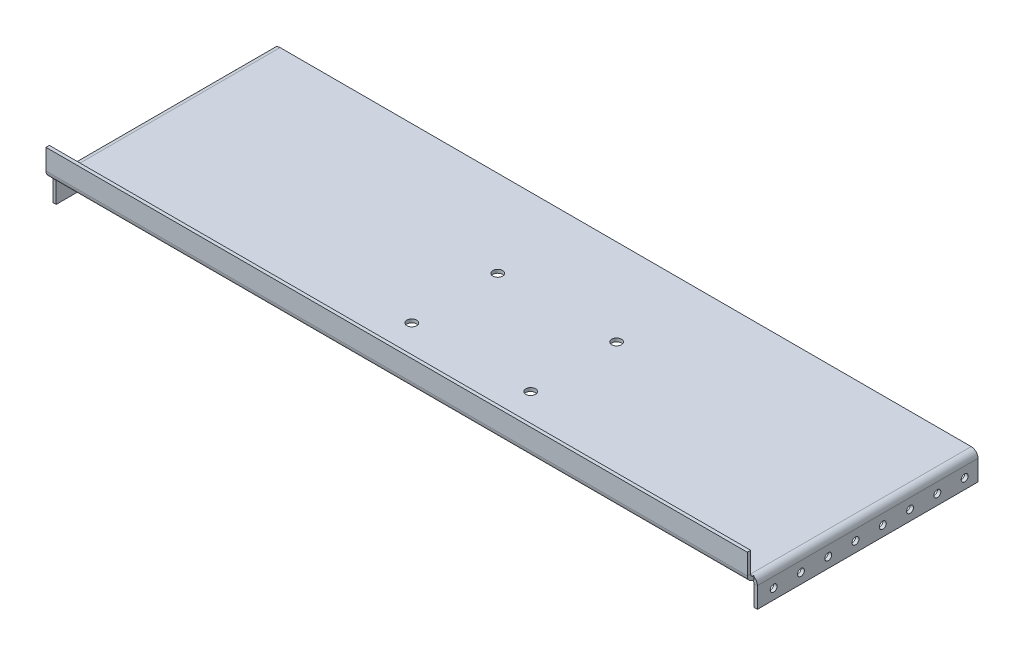
SolidWorks part; units mm, degrees
note: The reader was unsure of these and kept them because the rebuilt part matched: flange length of "Edge-Flange1", "Edge-Flange2", "Edge-Flange3".
ref_plane "Front Plane" through (0, 0, 0) normal (0, 0, 1) x (1, 0, 0)
ref_plane "Top Plane" through (0, 0, 0) normal (0, 1, 0) x (1, 0, 0)
ref_plane "Right Plane" through (0, 0, 0) normal (1, 0, 0) x (0, 0, -1)
sketch "Sketch1" plane through (0, 0, 0) normal (0, 1, 0) x (1, 0, 0)
  line L1 (244.844, -88.9) -> (-244.844, -88.9)
  line L2 (244.844, -88.9) -> (244.844, 88.9)
  line L3 (244.844, 88.9) -> (-244.844, 88.9)
  line L4 (-244.844, -88.9) -> (-244.844, 88.9)
  line L5 (244.844, -88.9) -> (-244.844, 88.9) construction
  line L6 (244.844, 88.9) -> (-244.844, -88.9) construction
  point P0 (0, 0)
  dimension "D1" = 489.688
  dimension "D2" = 177.8
base flange "Base-Flange1" sketch "Sketch1" thickness 2.3622 reverse thickness direction no parameters "D1"=10
edge flange "Edge-Flange1" sketch "Sketch8" flange angle 90 flange length 19.05 flange position material inside bend radius 2.36 thickness 2.3622 relief rectangular parameters "D6"=10
sketch "Sketch8" plane through (0, 0, 88.9) normal (0, 0, 1) x (1, 0, 0)
  line L2 (-244.844, 0) -> (-244.844, 16.6878)
  line L3 (-244.844, 16.6878) -> (244.844, 16.6878)
  line L4 (244.844, 16.6878) -> (244.844, 0)
  line L11 (-244.844, 0) -> (244.844, 0) construction
  line L12 (-244.844, 0) -> (244.844, 0)
bend "EdgeBend1" bend radius 2.36 bend angle 90 parameters "D5"=1
edge flange "Edge-Flange2" sketch "Sketch11" flange angle 90 flange length 19.05 flange position material inside bend radius 2.36 thickness 2.3622 relief none parameters "D6"=10
sketch "Sketch11" plane through (-244.844, -2.3622, 0) normal (-1, 0, 0) x (0, 0, -1)
  line L0 (88.9, 0) -> (-84.1778, 0) construction
  line L1 (88.9, 0) -> (-84.1778, 0)
  line L2 (-84.1778, 0) -> (-84.1778, 16.6878)
  line L3 (-84.1778, 16.6878) -> (88.9, 16.6878)
  line L4 (88.9, 16.6878) -> (88.9, 0)
bend "EdgeBend2" bend radius 2.36 bend angle 90 parameters "D5"=2
edge flange "Edge-Flange3" sketch "Sketch14" flange angle 90 flange length 19.05 flange position material outside bend radius 2.36 thickness 2.3622 relief none parameters "D6"=10
sketch "Sketch14" plane through (244.844, -2.3622, 0) normal (1, 0, 0) x (0, 0, 1)
  line L2 (-88.9, 0) -> (-88.9, 16.6878)
  line L3 (-88.9, 16.6878) -> (84.1778, 16.6878)
  line L4 (84.1778, 16.6878) -> (84.1778, 0)
  line L7 (84.1778, 0) -> (-88.9, 0) construction
  line L8 (84.1778, 0) -> (-88.9, 0)
bend "EdgeBend3" bend radius 2.36 bend angle 90 parameters "D5"=3
sketch "Sketch15" plane through (0, 0, 0) normal (0, 1, 0) x (1, 0, 0)
  line L0 (242.484, -84.1778) -> (-240.1218, -84.1778) construction
  line L1 (-27.6218, 9.3222) -> (55.3782, 9.3222) construction
  line L2 (-27.6218, 9.3222) -> (-27.6218, -50.6778) construction
  line L3 (-27.6218, -50.6778) -> (55.3782, -50.6778) construction
  line L4 (55.3782, 9.3222) -> (55.3782, -50.6778) construction
  line L5 (-27.6218, 9.3222) -> (55.3782, -50.6778) construction
  line L6 (-27.6218, -50.6778) -> (55.3782, 9.3222) construction
  line L7 (-240.1218, 88.9) -> (-240.1218, -84.1778) construction
  circle A0 centre (-27.6218, 9.3222) radius 3.4
  circle A1 centre (-27.6218, -50.6778) radius 3.4
  circle A2 centre (55.3782, 9.3222) radius 3.4
  circle A3 centre (55.3782, -50.6778) radius 3.4
  point P0 (13.8782, -20.6778)
  dimension "D3" = 6.8
  dimension "D1" = 83
  dimension "D2" = 60
  dimension "D4" = 63.5
  dimension "D5" = 254
extrude "Cut-Extrude1" cut sketch "Sketch15" against normal blind 6.35 normal cut yes
sketch "Sketch33" plane through (0, 0, 0) normal (0, 1, 0) x (1, 0, 0)
  line L0 (242.484, 88.9) -> (-240.1218, 88.9) construction
  line L1 (268.5996, 69.85) -> (-266.2374, 69.85)
  line L2 (268.5996, 69.85) -> (268.5996, 107.95)
  line L3 (268.5996, 107.95) -> (-266.2374, 107.95)
  line L4 (-266.2374, 69.85) -> (-266.2374, 107.95)
  line L5 (268.5996, 69.85) -> (-266.2374, 107.95) construction
  line L6 (268.5996, 107.95) -> (-266.2374, 69.85) construction
  point P0 (1.1811, 88.9)
  dimension "D1" = 38.1
extrude "Cut-Extrude5" cut sketch "Sketch33" against normal through all normal cut yes
sketch "Sketch37" plane through (-244.844, 0, 0) normal (-1, 0, 0) x (0, 0, 1)
  circle A0 centre (72.824, -11.8861) radius 2.413
  circle A1 centre (53.774, -11.8861) radius 2.413
  circle A2 centre (34.724, -11.8861) radius 2.413
  circle A3 centre (15.674, -11.8861) radius 2.413
  circle A4 centre (-3.376, -11.8861) radius 2.413
  circle A5 centre (-22.426, -11.8861) radius 2.413
  circle A6 centre (-41.476, -11.8861) radius 2.413
  circle A7 centre (-60.526, -11.8861) radius 2.413
  circle A9 centre (72.824, -11.8861) radius 2.413 construction
  circle A10 centre (53.774, -11.8861) radius 2.413 construction
  circle A11 centre (34.724, -11.8861) radius 2.413 construction
  circle A12 centre (15.674, -11.8861) radius 2.413 construction
  circle A13 centre (-3.376, -11.8861) radius 2.413 construction
  circle A14 centre (-60.526, -11.8861) radius 2.413 construction
  circle A15 centre (-41.476, -11.8861) radius 2.413 construction
  circle A16 centre (-22.426, -11.8861) radius 2.413 construction
extrude "Cut-Extrude8" cut sketch "Sketch37" against normal through all normal cut yes
sketch "Bend-Lines1" [suppressed] plane through (0, 0, 0) normal (0, 1, 0) x (1, 0, 0)
sketch "Bounding-Box1" [suppressed] plane through (0, 0, 0) normal (0, 1, 0) x (1, 0, 0)
sheet metal parameters "Sheet-Metal1" thickness 2.3622 parameters "D1"=10
flat pattern "Flat-Pattern1" [suppressed]
sketch "Bend-Lines2" plane through (0, 0, 0) normal (0, 1, 0) x (1, 0, 0)
sketch3d "Bounding-Box2" [suppressed]
  line L0 (-255.27, -88.9, 0) -> (255.27, -88.9, 0) construction
  line L1 (-255.27, 88.9, 0) -> (255.27, 88.9, 0) construction
  line L2 (-255.27, -88.9, 0) -> (-255.27, 88.9, 0) construction
  line L3 (255.27, -88.9, 0) -> (255.27, 88.9, 0) construction
sheet metal parameters "Sheet-Metal2" thickness 2.3622 parameters "D1"=10
flat pattern "Flat-Pattern1"
sketch "Bend-Lines2" plane through (0, 0, 0) normal (0, 1, 0) x (1, 0, 0)
  line L0 (-255.27, -86.959) -> (255.27, -86.959) construction
  line L1 (-255.27, -86.959) -> (255.27, -86.959) construction
sketch3d "Bounding-Box2" [suppressed]
  line L0 (255.27, -104.0679, 0) -> (-255.27, -104.0679, 0) construction
  line L1 (255.27, 88.9, 0) -> (-255.27, 88.9, 0) construction
  line L2 (255.27, -104.0679, 0) -> (255.27, 88.9, 0) construction
  line L3 (-255.27, -104.0679, 0) -> (-255.27, 88.9, 0) construction
bend of the flat pattern "Flatten-<EdgeBend1>1"
sheet metal parameters "Sheet-Metal3" thickness 2.3622 parameters "D1"=10
flat pattern "Flat-Pattern1"
sketch "Bend-Lines2" plane through (0, 0, 0) normal (0, 1, 0) x (1, 0, 0)
  line L0 (-255.27, -86.959) -> (255.27, -86.959) construction
  line L1 (-255.27, -86.959) -> (255.27, -86.959) construction
  line L2 (-253.329, 88.9) -> (-253.329, -84.1778) construction
  line L3 (-253.329, 88.9) -> (-253.329, -84.1778) construction
sketch3d "Bounding-Box2" [suppressed]
  line L0 (255.27, -104.0679, 0) -> (-270.4379, -104.0679, 0) construction
  line L1 (255.27, 88.9, 0) -> (-270.4379, 88.9, 0) construction
  line L2 (255.27, -104.0679, 0) -> (255.27, 88.9, 0) construction
  line L3 (-270.4379, -104.0679, 0) -> (-270.4379, 88.9, 0) construction
bend of the flat pattern "Flatten-<EdgeBend1>1"
bend of the flat pattern "Flatten-<EdgeBend2>1"
sheet metal parameters "Sheet-Metal4" thickness 2.3622 parameters "D1"=10
flat pattern "Flat-Pattern1"
sketch "Bend-Lines2" plane through (0, 0, 0) normal (0, 1, 0) x (1, 0, 0)
  line L0 (-244.844, -86.959) -> (244.844, -86.959) construction
  line L1 (-244.844, -86.959) -> (244.844, -86.959) construction
  line L2 (-242.903, 88.9) -> (-242.903, -84.1778) construction
  line L3 (-242.903, 88.9) -> (-242.903, -84.1778) construction
  line L4 (245.2652, -84.1778) -> (245.2652, 88.9) construction
  line L5 (245.2652, -84.1778) -> (245.2652, 88.9) construction
sketch3d "Bounding-Box2" [suppressed]
  line L0 (262.3741, -104.0679, 0) -> (-260.0119, -104.0679, 0) construction
  line L1 (262.3741, 88.9, 0) -> (-260.0119, 88.9, 0) construction
  line L2 (262.3741, -104.0679, 0) -> (262.3741, 88.9, 0) construction
  line L3 (-260.0119, -104.0679, 0) -> (-260.0119, 88.9, 0) construction
bend of the flat pattern "Flatten-<EdgeBend1>1"
bend of the flat pattern "Flatten-<EdgeBend2>1"
bend of the flat pattern "Flatten-<EdgeBend3>1"
sheet metal parameters "Sheet-Metal5" thickness 2.3622 parameters "D1"=10
flat pattern "Flat-Pattern1"
sketch "Bend-Lines2" plane through (0, 0, 0) normal (0, 1, 0) x (1, 0, 0)
  line L0 (-244.844, -86.959) -> (244.844, -86.959) construction
  line L1 (-244.844, -86.959) -> (244.844, -86.959) construction
  line L2 (-242.903, 88.9) -> (-242.903, -84.1778) construction
  line L3 (-242.903, 88.9) -> (-242.903, -84.1778) construction
  line L4 (245.2652, -84.1778) -> (245.2652, 88.9) construction
  line L5 (245.2652, -84.1778) -> (245.2652, 88.9) construction
sketch3d "Bounding-Box2" [suppressed]
  line L0 (262.3741, -104.0679, 0) -> (-260.0119, -104.0679, 0) construction
  line L1 (262.3741, 88.9, 0) -> (-260.0119, 88.9, 0) construction
  line L2 (262.3741, -104.0679, 0) -> (262.3741, 88.9, 0) construction
  line L3 (-260.0119, -104.0679, 0) -> (-260.0119, 88.9, 0) construction
bend of the flat pattern "Flatten-<EdgeBend1>1"
bend of the flat pattern "Flatten-<EdgeBend2>1"
bend of the flat pattern "Flatten-<EdgeBend3>1"
sheet metal parameters "Sheet-Metal13" thickness 2.3622 parameters "D1"=10
flat pattern "Flat-Pattern1"
sketch "Bend-Lines2" plane through (0, 0, 0) normal (0, 1, 0) x (1, 0, 0)
  line L0 (245.2652, -84.1778) -> (245.2652, 69.85) construction
  line L1 (-242.903, 69.85) -> (-242.903, -84.1778) construction
  line L2 (-244.844, -86.959) -> (244.844, -86.959) construction
  line L3 (245.2652, -84.1778) -> (245.2652, 69.85) construction
  line L4 (-242.903, 69.85) -> (-242.903, -84.1778) construction
  line L5 (-244.844, -86.959) -> (244.844, -86.959) construction
sketch3d "Bounding-Box2" [suppressed]
  line L0 (262.3741, -104.0679, 0) -> (-260.0119, -104.0679, 0) construction
  line L1 (262.3741, 69.85, 0) -> (-260.0119, 69.85, 0) construction
  line L2 (262.3741, -104.0679, 0) -> (262.3741, 69.85, 0) construction
  line L3 (-260.0119, -104.0679, 0) -> (-260.0119, 69.85, 0) construction
bend of the flat pattern "Flatten-<EdgeBend3>2"
bend of the flat pattern "Flatten-<EdgeBend2>2"
bend of the flat pattern "Flatten-<EdgeBend1>2"
sheet metal parameters "Sheet-Metal16" thickness 2.3622 parameters "D1"=10
flat pattern "Flat-Pattern1"
sketch "Bend-Lines2" plane through (0, 0, 0) normal (0, 1, 0) x (1, 0, 0)
  line L0 (245.2652, -84.1778) -> (245.2652, 69.85) construction
  line L1 (-242.903, 69.85) -> (-242.903, -84.1778) construction
  line L2 (-244.844, -86.959) -> (244.844, -86.959) construction
  line L3 (245.2652, -84.1778) -> (245.2652, 69.85) construction
  line L4 (-242.903, 69.85) -> (-242.903, -84.1778) construction
  line L5 (-244.844, -86.959) -> (244.844, -86.959) construction
sketch3d "Bounding-Box2" [suppressed]
  line L0 (262.3741, -104.0679, 0) -> (-260.0119, -104.0679, 0) construction
  line L1 (262.3741, 69.85, 0) -> (-260.0119, 69.85, 0) construction
  line L2 (262.3741, -104.0679, 0) -> (262.3741, 69.85, 0) construction
  line L3 (-260.0119, -104.0679, 0) -> (-260.0119, 69.85, 0) construction
bend of the flat pattern "Flatten-<EdgeBend3>2"
bend of the flat pattern "Flatten-<EdgeBend2>2"
bend of the flat pattern "Flatten-<EdgeBend1>2"
